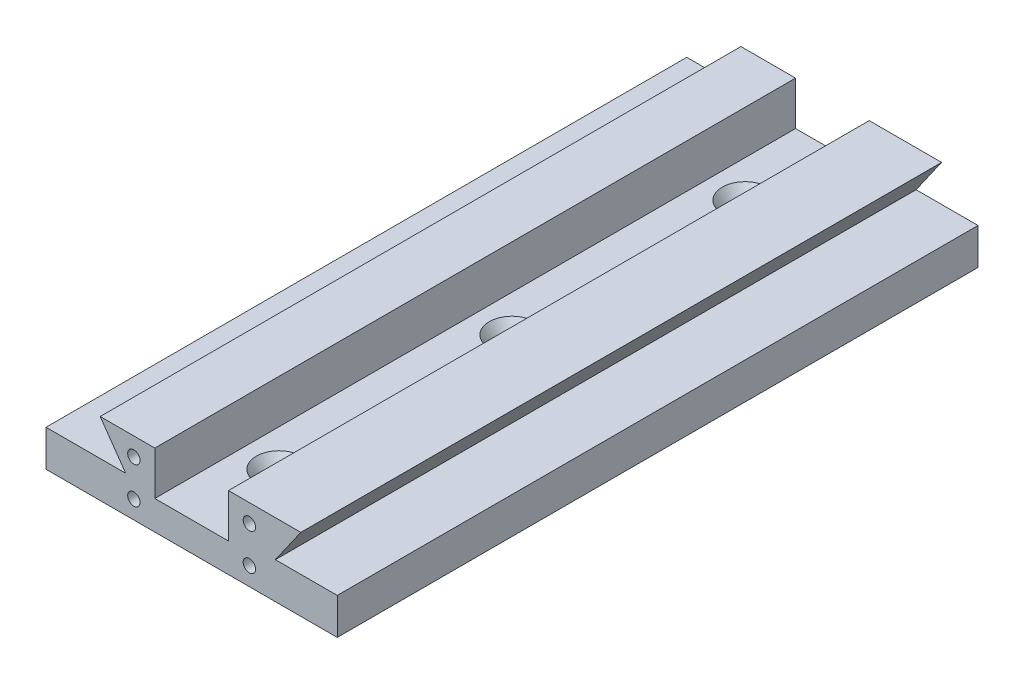
SolidWorks part; units mm, degrees
material "Ductile Iron"
ref_plane "Front Plane" through (0, 0, 0) normal (0, 0, 1) x (1, 0, 0)
ref_plane "Top Plane" through (0, 0, 0) normal (0, 1, 0) x (1, 0, 0)
ref_plane "Right Plane" through (0, 0, 0) normal (1, 0, 0) x (0, 0, -1)
sketch "dovetail-male-profile" plane through (0, 0, 0) normal (0, 0, 1) x (1, 0, 0)
  line L0 (0, 0) -> (127, 0)
  line L1 (127, 0) -> (127, 15.875)
  line L2 (127, 15.875) -> (100.0092, 15.875) construction
  line L3 (100.0092, 15.875) -> (111.125, 31.75)
  line L4 (111.125, 31.75) -> (15.875, 31.75) construction
  line L5 (15.875, 31.75) -> (26.9908, 15.875) construction
  line L6 (26.9908, 15.875) -> (0, 15.875)
  line L7 (0, 15.875) -> (0, 0)
  line L8 (111.125, 31.75) -> (23.6269, 31.75)
  line L10 (100.0092, 15.875) -> (127, 15.875)
  line L11 (23.6269, 31.75) -> (34.7427, 15.875)
  line L12 (34.7427, 15.875) -> (26.9908, 15.875)
  dimension "D1" = 127
  dimension "D2" = 55
  dimension "D3" = 95.25
  dimension "D4" = 55
  dimension "D5" = 31.75
  dimension "D6" = 15.875
  dimension "D7" = 6.35
extrude "x-guide-extrude" add sketch "dovetail-male-profile" along normal blind 279.4
sketch "Sketch1" plane through (0, 0, 0) normal (0, 0, 1) x (1, 0, 0)
  line L0 (47.4437, 31.75) -> (47.4437, 12.7)
  line L2 (47.4437, 12.7) -> (79.5563, 12.7)
  line L3 (79.5563, 12.7) -> (79.5563, 31.75)
  line L4 (63.5, 0) -> (63.5, 31.75) construction
  line L5 (111.125, 31.75) -> (23.6269, 31.75) construction
  line L6 (47.4437, 31.75) -> (79.5563, 31.75)
  line L7 (0, 0) -> (127, 0) construction
  circle A0 centre (63.5, 22.225) radius 18.669 construction
  point P12 (63.5, 0)
  dimension "D1" = 37.338
  dimension "D2" = 19.05
extrude "Cut-Extrude1" cut sketch "Sketch1" along normal through all contours L6 L0 L2 L3 region at (63.5, 22.225, 0)
hole_wizard "1/4-20 Tapped Hole1" positions "Sketch2" profile "Sketch3" tap size "1/4-20" standard "ANSI Inch"
sketch "Sketch2" plane through (0, 0, 0) normal (0, 0, -1) x (-1, 0, 0)
  line L0 (-63.5, 31.75) -> (-63.5, 0) construction
  line L3 (-103.3731, 15.875) -> (-34.7427, 15.875) construction
  line L5 (-29.1848, 23.8125) -> (-47.4437, 23.8125) construction
  line L6 (-88.6858, 23.8125) -> (-38.3142, 23.8125) construction
  line L7 (-88.6858, 23.8125) -> (-88.6858, 7.9375) construction
  line L8 (-88.6858, 7.9375) -> (-38.3142, 7.9375) construction
  line L9 (-38.3142, 23.8125) -> (-38.3142, 7.9375) construction
  point P0 (-88.6858, 23.8125)
  point P1 (-88.6858, 7.9375)
  point P2 (-38.3142, 7.9375)
  point P3 (-38.3142, 23.8125)
sketch "Sketch3" plane through (88.6858, 23.8125, 0) normal (1, 0, 0) x (0, 1, 0)
  line L0 (0, 0) -> (0, 18.0438)
  line L1 (0, 18.0438) -> (2.5527, 16.51)
  line L2 (2.5527, 16.51) -> (2.5527, 0)
  line L3 (2.5527, 0) -> (0, 0)
  line L4 (0, 18.0438) -> (-2.5527, 16.51) construction
  line L5 (0, -6.35) -> (0, 107.95) construction
  dimension "Tap Drill Dia." = 5.1054
  dimension "Tap Drill Depth" = 16.51
  dimension "Drill Angle" = 118
cosmetic thread "Hole Thread1" parameters "D1"=12.7, "D2"=6.35
cosmetic thread "Hole Thread2" parameters "D1"=12.7, "D2"=6.35
cosmetic thread "Hole Thread3" parameters "D1"=12.7, "D2"=6.35
cosmetic thread "Hole Thread4" parameters "D1"=12.7, "D2"=6.35
hole_wizard "1/4-28 Tapped Hole1" positions "Sketch4" profile "Sketch5" tap size "1/4-28" standard "ANSI Inch"
sketch "Sketch4" plane through (0, 0, 279.4) normal (0, 0, 1) x (1, 0, 0)
  point P0 (38.3142, 23.8125)
  point P1 (38.3142, 7.9375)
  point P2 (88.6858, 7.9375)
  point P3 (88.6858, 23.8125)
sketch "Sketch5" plane through (38.3142, 23.8125, 279.4) normal (1, 0, 0) x (0, -1, 0)
  line L0 (0, 0) -> (0, 18.1354)
  line L1 (0, 18.1354) -> (2.7051, 16.51)
  line L2 (2.7051, 16.51) -> (2.7051, 0)
  line L3 (2.7051, 0) -> (0, 0)
  line L4 (0, 18.1354) -> (-2.7051, 16.51) construction
  line L5 (0, -6.35) -> (0, 107.95) construction
  dimension "Tap Drill Dia." = 5.4102
  dimension "Tap Drill Depth" = 16.51
  dimension "Drill Angle" = 118
cosmetic thread "Hole Thread5" parameters "D1"=12.7, "D2"=6.35
cosmetic thread "Hole Thread6" parameters "D1"=12.7, "D2"=6.35
cosmetic thread "Hole Thread7" parameters "D1"=12.7, "D2"=6.35
cosmetic thread "Hole Thread8" parameters "D1"=12.7, "D2"=6.35
hole_wizard "bed mount CSK for 3/8 Flat Head Socket Cap Screw1" positions "Sketch7" profile "Sketch6" countersink size "3/8" standard "ANSI Inch" end condition up to next
sketch "Sketch7" plane through (0, 12.7, 0) normal (0, 1, 0) x (1, 0, 0)
  line L0 (63.5, -279.4) -> (63.5, 0) construction
  line L1 (47.4437, -279.4) -> (79.5563, -279.4) construction
  line L2 (47.4437, 0) -> (79.5563, 0) construction
  point P0 (63.5, -38.1)
  point P2 (63.5, -139.7)
  point P4 (63.5, -241.3)
  dimension "D1" = 101.6
  dimension "D2" = 101.6
sketch "Sketch6" plane through (63.5, 12.7, 38.1) normal (1, 0, 0) x (0, 0, 1)
  line L0 (0, 0) -> (0, 12.7)
  line L1 (0, 12.7) -> (5.0419, 12.7)
  line L2 (5.0419, 12.7) -> (5.0419, 5.6101)
  line L3 (5.0419, 5.6101) -> (9.9187, 0)
  line L5 (9.9187, 0) -> (0, 0)
  line L6 (-5.0419, 5.6101) -> (-9.9187, 0) construction
  line L11 (0, -6.35) -> (0, 107.95) construction
  dimension "Thru Hole Dia." = 10.0838
  dimension "Thru Hole Depth" = 12.7
  dimension "Near C'Sink Dia." = 19.8374
  dimension "Near C'Sink Angle" = 82
equation "\"dovetail-angle\"= 55"
equation "\"dovetail-stock-width\"= 5"
equation "\"dovetail-stock-height\"= 1.25"
equation "\"D1@dovetail-male-profile\"=\"dovetail-stock-width\""
equation "\"dovetail-throat-width\"= \"dovetail-stock-width\" - (2 * \"dovetail-depth\")"
equation "\"D3@dovetail-male-profile\"=\"dovetail-throat-width\""
equation "\"dovetail-depth\"= 0.5 * \"dovetail-stock-height\""
equation "\"D2@dovetail-male-profile\"=\"dovetail-angle\""
equation "\"D4@dovetail-male-profile\"=\"dovetail-angle\""
equation "\"D5@dovetail-male-profile\"=\"dovetail-stock-height\""
equation "\"D6@dovetail-male-profile\"=\"dovetail-depth\""
equation "\"delta-x\"= 6"
equation "\"delta-y\"= 3"
equation "\"gib-thickness\"= 0.25"
equation "\"x-slide-length\"= \"dovetail-stock-width\" + \"delta-x\""
equation "\"y-slide-length\"= \"dovetail-stock-width\" + \"delta-y\""
equation "\"D1@x-guide-extrude\"=\"x-slide-length\""
equation "\"D7@dovetail-male-profile\"=\"gib-thickness\""
equation "\"dog-point-diam\"= .149"
equation "\"dog-point-length\"= .067"
equation "\"dovetail-double-height\"= 2 * \"dovetail-depth\" + 0.5"
equation "\"acme-major-diam\"= .5"
equation "\"acme-pitch-diam\"= 0.45"
equation "\"acme-minor-diam\"= 0.4"
equation "\"acme-nut-od\"= 1.47"
equation "\"acme-nut-length\"= 1"
equation "\"acme-nut-trim-height\"= .75"
equation "\"screw-bearing-od\"= 0.5"
equation "\"screw-bearing-length\"= .25"
equation "\"end-plate-thickness\"= \"screw-bearing-length\""
equation "\"D1@Sketch1\"=\"acme-nut-od\""
equation "\"D2@Sketch1\"=\"acme-nut-trim-height\""
equation "\"screw-bearing-id\"= .375"
equation "\"screw-add-length\"= 2 * \"end-plate-thickness\" + 1 + 0.5"
equation "\"acme-nut-mount-hole-space-horz\"= 0.82"
equation "\"acme-nut-mount-hole-space-vert\"= 0.5 * \"acme-nut-length\""
equation "\"x-screw-length\"= \"x-slide-length\" + \"screw-add-length\""
equation "\"y-screw-length\"= \"y-slide-length\" + \"screw-add-length\""
